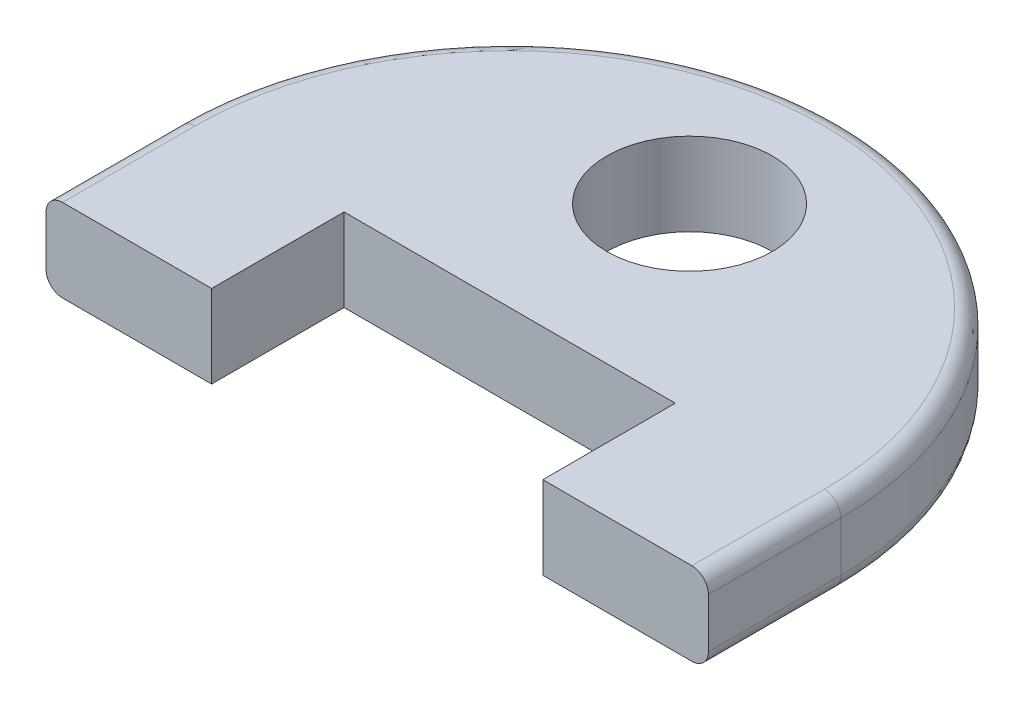
SolidWorks part; units mm, degrees
ref_plane "Front Plane" through (0, 0, 0) normal (0, 0, 1) x (1, 0, 0)
ref_plane "Top Plane" through (0, 0, 0) normal (0, 1, 0) x (1, 0, 0)
ref_plane "Right Plane" through (0, 0, 0) normal (1, 0, 0) x (0, 0, -1)
sketch "Sketch1" plane through (0, 0, 0) normal (0, 1, 0) x (1, 0, 0)
  line L1 (-25.4, -10.16) -> (-12.7, -10.16)
  line L2 (-25.4, -10.16) -> (-25.4, 0)
  line L4 (25.4, -10.16) -> (25.4, 0)
  line L8 (-12.7, -10.16) -> (-12.7, 0)
  line L9 (-12.7, 0) -> (12.7, 0)
  line L10 (12.7, -10.16) -> (12.7, 0)
  line L11 (12.7, -10.16) -> (25.4, -10.16)
  arc A0 (-25.4, 0) -> (25.4, 0) centre (0, 0) cw
  point P0 (0, 0)
  point P11 (1.0059, 1.1289)
  point P12 (0, 0)
  dimension "D1" = 25.4
  dimension "D2" = 12.7
  dimension "D3" = 12.7
  dimension "D4" = 10.16
extrude "Boss-Extrude1" add sketch "Sketch1" along normal blind 6.35
fillet "Fillet2" radius 1.27 6 edges at (25.4, 0, 5.08) (-25.4, 0, 5.08) (25.4, 6.35, 5.08) (-25.4, 6.35, 5.08) (0, 0, -25.4) (0, 6.35, -25.4)
sketch "Sketch2" plane through (0, 6.35, 0) normal (0, 1, 0) x (1, 0, 0)
  circle A0 centre (0, 13.7961) radius 6.35
  dimension "D1" = 12.7
extrude "Cut-Extrude1" cut sketch "Sketch2" against normal through all
